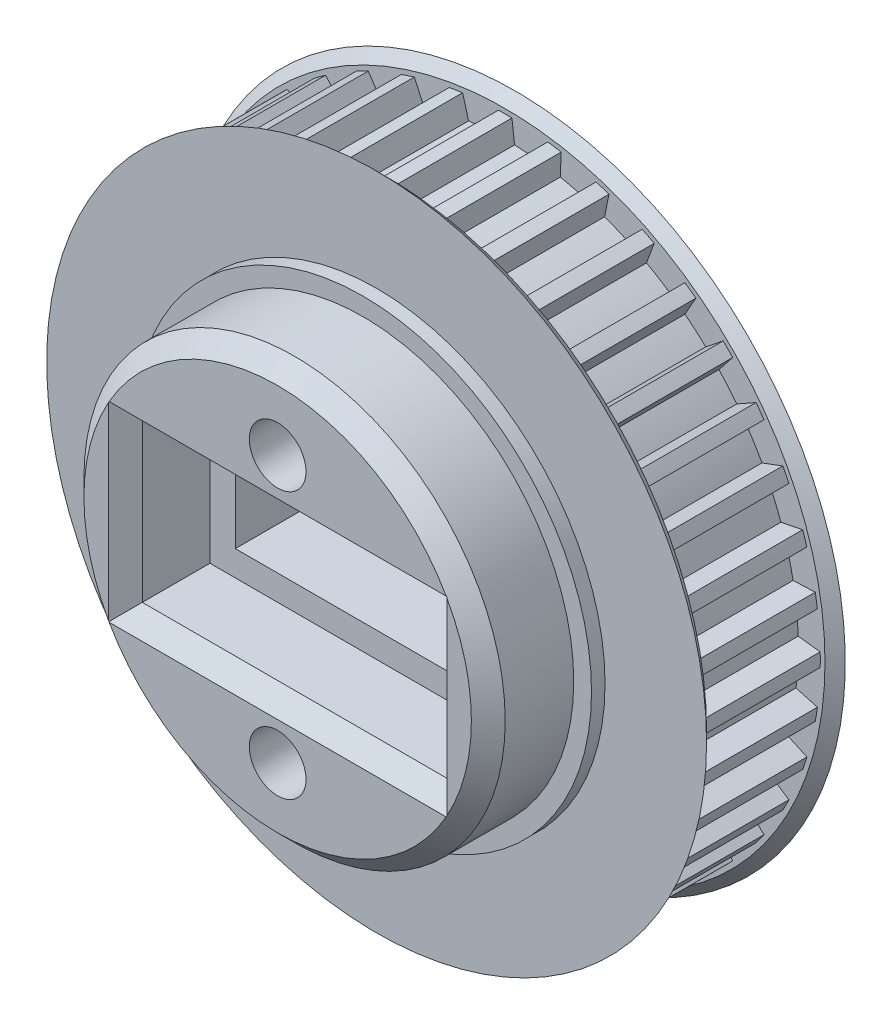
SolidWorks part; units mm, degrees
material "ABS"
ref_plane "Alzado" through (0, 0, 0) normal (0, 0, 1) x (1, 0, 0)
ref_plane "Planta" through (0, 0, 0) normal (0, 1, 0) x (1, 0, 0)
ref_plane "Vista lateral" through (0, 0, 0) normal (1, 0, 0) x (0, 0, -1)
sketch "Croquis1" plane through (0, 0, 0) normal (0, 0, 1) x (1, 0, 0)
  line L0 (0, 0) -> (0, 14.5885) construction
  line L1 (-0.4, 18.6167) -> (-0.55, 17.3123)
  line L2 (0.4, 18.6167) -> (0.55, 17.3123)
  line L3 (3.3074, 18.3249) -> (3.2515, 17.0131)
  line L4 (2.5172, 18.4501) -> (2.165, 17.1852)
  line L5 (6.1333, 17.5819) -> (5.8729, 16.295)
  line L6 (5.3725, 17.8291) -> (4.8267, 16.6349)
  line L7 (8.8082, 16.406) -> (8.3497, 15.1756)
  line L8 (8.0954, 16.7692) -> (7.3695, 15.675)
  line L9 (11.2662, 14.8261) -> (10.6209, 13.6826)
  line L10 (10.619, 15.2963) -> (9.7309, 14.3292)
  line L11 (13.4468, 12.8812) -> (12.6305, 11.8527)
  line L12 (12.8812, 13.4468) -> (11.8527, 12.6305)
  line L13 (15.2963, 10.619) -> (14.3292, 9.7309)
  line L14 (14.8261, 11.2662) -> (13.6826, 10.6209)
  line L15 (16.7692, 8.0954) -> (15.675, 7.3695)
  line L16 (16.406, 8.8082) -> (15.1756, 8.3497)
  line L17 (17.8291, 5.3725) -> (16.6349, 4.8267)
  line L18 (17.5819, 6.1333) -> (16.295, 5.8729)
  line L19 (18.4501, 2.5172) -> (17.1852, 2.165)
  line L20 (18.3249, 3.3074) -> (17.0131, 3.2515)
  line L21 (18.6167, -0.4) -> (17.3123, -0.55)
  line L22 (18.6167, 0.4) -> (17.3123, 0.55)
  line L23 (18.3249, -3.3074) -> (17.0131, -3.2515)
  line L24 (18.4501, -2.5172) -> (17.1852, -2.165)
  line L25 (17.5819, -6.1333) -> (16.295, -5.8729)
  line L26 (17.8291, -5.3725) -> (16.6349, -4.8267)
  line L27 (16.406, -8.8082) -> (15.1756, -8.3497)
  line L28 (16.7692, -8.0954) -> (15.675, -7.3695)
  line L29 (14.8261, -11.2662) -> (13.6826, -10.6209)
  line L30 (15.2963, -10.619) -> (14.3292, -9.7309)
  line L31 (12.8812, -13.4468) -> (11.8527, -12.6305)
  line L32 (13.4468, -12.8812) -> (12.6305, -11.8527)
  line L33 (10.619, -15.2963) -> (9.7309, -14.3292)
  line L34 (11.2662, -14.8261) -> (10.6209, -13.6826)
  line L35 (8.0954, -16.7692) -> (7.3695, -15.675)
  line L36 (8.8082, -16.406) -> (8.3497, -15.1756)
  line L37 (5.3725, -17.8291) -> (4.8267, -16.6349)
  line L38 (6.1333, -17.5819) -> (5.8729, -16.295)
  line L39 (2.5172, -18.4501) -> (2.165, -17.1852)
  line L40 (3.3074, -18.3249) -> (3.2515, -17.0131)
  line L41 (-0.4, -18.6167) -> (-0.55, -17.3123)
  line L42 (0.4, -18.6167) -> (0.55, -17.3123)
  line L43 (-3.3074, -18.3249) -> (-3.2515, -17.0131)
  line L44 (-2.5172, -18.4501) -> (-2.165, -17.1852)
  line L45 (-6.1333, -17.5819) -> (-5.8729, -16.295)
  line L46 (-5.3725, -17.8291) -> (-4.8267, -16.6349)
  line L47 (-8.8082, -16.406) -> (-8.3497, -15.1756)
  line L48 (-8.0954, -16.7692) -> (-7.3695, -15.675)
  line L49 (-11.2662, -14.8261) -> (-10.6209, -13.6826)
  line L50 (-10.619, -15.2963) -> (-9.7309, -14.3292)
  line L51 (-13.4468, -12.8812) -> (-12.6305, -11.8527)
  line L52 (-12.8812, -13.4468) -> (-11.8527, -12.6305)
  line L53 (-15.2963, -10.619) -> (-14.3292, -9.7309)
  line L54 (-14.8261, -11.2662) -> (-13.6826, -10.6209)
  line L55 (-16.7692, -8.0954) -> (-15.675, -7.3695)
  line L56 (-16.406, -8.8082) -> (-15.1756, -8.3497)
  line L57 (-17.8291, -5.3725) -> (-16.6349, -4.8267)
  line L58 (-17.5819, -6.1333) -> (-16.295, -5.8729)
  line L59 (-18.4501, -2.5172) -> (-17.1852, -2.165)
  line L60 (-18.3249, -3.3074) -> (-17.0131, -3.2515)
  line L61 (-18.6167, 0.4) -> (-17.3123, 0.55)
  line L62 (-18.6167, -0.4) -> (-17.3123, -0.55)
  line L63 (-18.3249, 3.3074) -> (-17.0131, 3.2515)
  line L64 (-18.4501, 2.5172) -> (-17.1852, 2.165)
  line L65 (-17.5819, 6.1333) -> (-16.295, 5.8729)
  line L66 (-17.8291, 5.3725) -> (-16.6349, 4.8267)
  line L67 (-16.406, 8.8082) -> (-15.1756, 8.3497)
  line L68 (-16.7692, 8.0954) -> (-15.675, 7.3695)
  line L69 (-14.8261, 11.2662) -> (-13.6826, 10.6209)
  line L70 (-15.2963, 10.619) -> (-14.3292, 9.7309)
  line L71 (-12.8812, 13.4468) -> (-11.8527, 12.6305)
  line L72 (-13.4468, 12.8812) -> (-12.6305, 11.8527)
  line L73 (-10.619, 15.2963) -> (-9.7309, 14.3292)
  line L74 (-11.2662, 14.8261) -> (-10.6209, 13.6826)
  line L75 (-8.0954, 16.7692) -> (-7.3695, 15.675)
  line L76 (-8.8082, 16.406) -> (-8.3497, 15.1756)
  line L77 (-5.3725, 17.8291) -> (-4.8267, 16.6349)
  line L78 (-6.1333, 17.5819) -> (-5.8729, 16.295)
  line L79 (-11.2662, 14.8261) -> (-10.619, 15.2963)
  line L80 (-8.8082, 16.406) -> (-8.0954, 16.7692)
  line L81 (-6.1333, 17.5819) -> (-5.3725, 17.8291)
  line L82 (-2.5172, 18.4501) -> (-2.165, 17.1852)
  line L83 (-3.3074, 18.3249) -> (-3.2515, 17.0131)
  line L84 (-3.3074, 18.3249) -> (-2.5172, 18.4501)
  arc A0 (-17.5819, 6.1333) -> (-17.8291, 5.3725) centre (0, 0) ccw
  arc A1 (2.165, 17.1852) -> (0.55, 17.3123) centre (0, 0) ccw
  arc A2 (-18.3249, 3.3074) -> (-18.4501, 2.5172) centre (0, 0) ccw
  arc A3 (-18.6167, 0.4) -> (-18.6167, -0.4) centre (0, 0) ccw
  arc A4 (-18.4501, -2.5172) -> (-18.3249, -3.3074) centre (0, 0) ccw
  arc A5 (-17.8291, -5.3725) -> (-17.5819, -6.1333) centre (0, 0) ccw
  arc A6 (-16.7692, -8.0954) -> (-16.406, -8.8082) centre (0, 0) ccw
  arc A7 (-15.2963, -10.619) -> (-14.8261, -11.2662) centre (0, 0) ccw
  arc A8 (-13.4468, -12.8812) -> (-12.8812, -13.4468) centre (0, 0) ccw
  arc A9 (-11.2662, -14.8261) -> (-10.619, -15.2963) centre (0, 0) ccw
  arc A10 (-8.8082, -16.406) -> (-8.0954, -16.7692) centre (0, 0) ccw
  arc A11 (3.3074, 18.3249) -> (2.5172, 18.4501) centre (0, 0) ccw
  arc A12 (0.4, 18.6167) -> (-0.4, 18.6167) centre (0, 0) ccw
  arc A13 (-14.8261, 11.2662) -> (-15.2963, 10.619) centre (0, 0) ccw
  arc A14 (-16.406, 8.8082) -> (-16.7692, 8.0954) centre (0, 0) ccw
  arc A15 (-12.8812, 13.4468) -> (-13.4468, 12.8812) centre (0, 0) ccw
  arc A16 (6.1333, 17.5819) -> (5.3725, 17.8291) centre (0, 0) ccw
  arc A17 (8.8082, 16.406) -> (8.0954, 16.7692) centre (0, 0) ccw
  arc A18 (11.2662, 14.8261) -> (10.619, 15.2963) centre (0, 0) ccw
  arc A19 (13.4468, 12.8812) -> (12.8812, 13.4468) centre (0, 0) ccw
  arc A20 (15.2963, 10.619) -> (14.8261, 11.2662) centre (0, 0) ccw
  arc A21 (16.7692, 8.0954) -> (16.406, 8.8082) centre (0, 0) ccw
  arc A22 (17.8291, 5.3725) -> (17.5819, 6.1333) centre (0, 0) ccw
  arc A23 (18.4501, 2.5172) -> (18.3249, 3.3074) centre (0, 0) ccw
  arc A24 (18.6167, -0.4) -> (18.6167, 0.4) centre (0, 0) ccw
  arc A25 (18.3249, -3.3074) -> (18.4501, -2.5172) centre (0, 0) ccw
  arc A26 (12.8812, -13.4468) -> (13.4468, -12.8812) centre (0, 0) ccw
  arc A27 (10.619, -15.2963) -> (11.2662, -14.8261) centre (0, 0) ccw
  arc A28 (8.0954, -16.7692) -> (8.8082, -16.406) centre (0, 0) ccw
  arc A29 (2.5172, -18.4501) -> (3.3074, -18.3249) centre (0, 0) ccw
  arc A30 (-0.4, -18.6167) -> (0.4, -18.6167) centre (0, 0) ccw
  arc A31 (-3.3074, -18.3249) -> (-2.5172, -18.4501) centre (0, 0) ccw
  arc A32 (-6.1333, -17.5819) -> (-5.3725, -17.8291) centre (0, 0) ccw
  arc A33 (14.8261, -11.2662) -> (15.2963, -10.619) centre (0, 0) ccw
  arc A34 (16.406, -8.8082) -> (16.7692, -8.0954) centre (0, 0) ccw
  arc A35 (17.5819, -6.1333) -> (17.8291, -5.3725) centre (0, 0) ccw
  arc A36 (4.8267, 16.6349) -> (3.2515, 17.0131) centre (0, 0) ccw
  arc A37 (7.3695, 15.675) -> (5.8729, 16.295) centre (0, 0) ccw
  arc A38 (-12.6305, 11.8527) -> (-13.6826, 10.6209) centre (0, 0) ccw
  arc A39 (-0.55, 17.3123) -> (-2.165, 17.1852) centre (0, 0) ccw
  arc A40 (-14.3292, 9.7309) -> (-15.1756, 8.3497) centre (0, 0) ccw
  arc A41 (-15.675, 7.3695) -> (-16.295, 5.8729) centre (0, 0) ccw
  arc A42 (-16.6349, 4.8267) -> (-17.0131, 3.2515) centre (0, 0) ccw
  arc A43 (9.7309, 14.3292) -> (8.3497, 15.1756) centre (0, 0) ccw
  arc A44 (11.8527, 12.6305) -> (10.6209, 13.6826) centre (0, 0) ccw
  arc A45 (13.6826, 10.6209) -> (12.6305, 11.8527) centre (0, 0) ccw
  arc A46 (15.1756, 8.3497) -> (14.3292, 9.7309) centre (0, 0) ccw
  arc A47 (16.295, 5.8729) -> (15.675, 7.3695) centre (0, 0) ccw
  arc A48 (17.0131, 3.2515) -> (16.6349, 4.8267) centre (0, 0) ccw
  arc A49 (17.3123, 0.55) -> (17.1852, 2.165) centre (0, 0) ccw
  arc A50 (17.1852, -2.165) -> (17.3123, -0.55) centre (0, 0) ccw
  arc A51 (16.6349, -4.8267) -> (17.0131, -3.2515) centre (0, 0) ccw
  arc A52 (15.675, -7.3695) -> (16.295, -5.8729) centre (0, 0) ccw
  arc A53 (14.3292, -9.7309) -> (15.1756, -8.3497) centre (0, 0) ccw
  arc A54 (12.6305, -11.8527) -> (13.6826, -10.6209) centre (0, 0) ccw
  arc A55 (10.6209, -13.6826) -> (11.8527, -12.6305) centre (0, 0) ccw
  arc A56 (8.3497, -15.1756) -> (9.7309, -14.3292) centre (0, 0) ccw
  arc A57 (5.8729, -16.295) -> (7.3695, -15.675) centre (0, 0) ccw
  arc A58 (3.2515, -17.0131) -> (4.8267, -16.6349) centre (0, 0) ccw
  arc A59 (0.55, -17.3123) -> (2.165, -17.1852) centre (0, 0) ccw
  arc A60 (-2.165, -17.1852) -> (-0.55, -17.3123) centre (0, 0) ccw
  arc A61 (-4.8267, -16.6349) -> (-3.2515, -17.0131) centre (0, 0) ccw
  arc A62 (-7.3695, -15.675) -> (-5.8729, -16.295) centre (0, 0) ccw
  arc A63 (-9.7309, -14.3292) -> (-8.3497, -15.1756) centre (0, 0) ccw
  arc A64 (-11.8527, -12.6305) -> (-10.6209, -13.6826) centre (0, 0) ccw
  arc A65 (-13.6826, -10.6209) -> (-12.6305, -11.8527) centre (0, 0) ccw
  arc A66 (-15.1756, -8.3497) -> (-14.3292, -9.7309) centre (0, 0) ccw
  arc A67 (-16.295, -5.8729) -> (-15.675, -7.3695) centre (0, 0) ccw
  arc A68 (-17.0131, -3.2515) -> (-16.6349, -4.8267) centre (0, 0) ccw
  arc A69 (-17.3123, -0.55) -> (-17.1852, -2.165) centre (0, 0) ccw
  arc A70 (-17.1852, 2.165) -> (-17.3123, 0.55) centre (0, 0) ccw
  arc A71 (5.3725, -17.8291) -> (6.1333, -17.5819) centre (0, 0) ccw
  circle A72 centre (0, 0) radius 2
  arc A73 (-5.8729, 16.295) -> (-7.3695, 15.675) centre (0, 0) ccw
  arc A74 (-8.3497, 15.1756) -> (-9.7309, 14.3292) centre (0, 0) ccw
  arc A75 (-10.6209, 13.6826) -> (-11.8527, 12.6305) centre (0, 0) ccw
  arc A76 (-3.2515, 17.0131) -> (-4.8267, 16.6349) centre (0, 0) ccw
  point P151 (0, 0)
  dimension "D1" = 1.3
  dimension "D6" = 4
  dimension "D2" = 1.1
  dimension "D3" = 0.8
  dimension "D5" = 1.62
  dimension "D4" = 40
extrude "Saliente-Extruir1" add sketch "Croquis1" along normal blind 7
sketch "Croquis2" plane through (0, 0, 7) normal (0, 0, 1) x (1, 0, 0)
  circle A0 centre (0, 0) radius 19.5
  circle A1 centre (0, 0) radius 2
  circle A2 centre (0, 0) radius 2 construction
  dimension "D1" = 39
extrude "Saliente-Extruir2" add sketch "Croquis2" along normal blind 0.6
sketch "Croquis3" plane through (0, 0, 7.6) normal (0, 0, 1) x (1, 0, 0)
  circle A0 centre (0, 0) radius 2
  circle A1 centre (0, 0) radius 12.45
  circle A3 centre (0, 0) radius 2 construction
  dimension "D1" = 24.9
sketch "Croquis4" plane through (0, 0, 0) normal (0, 0, -1) x (-1, 0, 0)
  circle A0 centre (0, 0) radius 2
  circle A1 centre (0, 0) radius 12.45
  circle A2 centre (0, 0) radius 2 construction
  dimension "D1" = 24.9
extrude "Saliente-Extruir4" add sketch "Croquis4" along normal blind 5.8
sketch "Croquis6" plane through (0, 0, 0) normal (0, 0, -1) x (-1, 0, 0)
  circle A0 centre (0, 0) radius 19.5
  circle A1 centre (0, 0) radius 2
  circle A2 centre (0, 0) radius 2 construction
  dimension "D1" = 39
extrude "Saliente-Extruir6" add sketch "Croquis6" along normal blind 0.6
sketch "Croquis5" plane through (0, 0, -0.6) normal (0, 0, -1) x (-1, 0, 0)
  circle A0 centre (0, 0) radius 2
  circle A1 centre (0, 0) radius 13.5
  circle A2 centre (0, 0) radius 2 construction
  dimension "D1" = 27
extrude "Saliente-Extruir5" add sketch "Croquis5" along normal blind 0.6
extrude "Saliente-Extruir7" add sketch "Croquis3" along normal blind 5.85
chamfer "Chaflán4" distance 1 angle 45 2 edges at (-12.45, 0, -5.8) (12.45, 0, 13.45)
sketch "Croquis7" plane through (0, 0, 7.6) normal (0, 0, 1) x (1, 0, 0)
  circle A0 centre (0, 0) radius 2
  circle A1 centre (0, 0) radius 13.5
  circle A2 centre (0, 0) radius 2 construction
  dimension "D1" = 27
extrude "Saliente-Extruir8" add sketch "Croquis7" along normal blind 0.8
sketch "Croquis8" plane through (0, 0, 0) normal (0, 0, 1) x (1, 0, 0)
  line L0 (0, 0) -> (6.706, 0) construction
  line L1 (-7.5, 3.15) -> (7.5, 3.15)
  line L2 (-7.5, 3.15) -> (-7.5, -3.15)
  line L3 (-7.5, -3.15) -> (7.5, -3.15)
  line L4 (7.5, 3.15) -> (7.5, -3.15)
  line L5 (-7.5, 3.15) -> (7.5, -3.15) construction
  line L6 (-7.5, -3.15) -> (7.5, 3.15) construction
  circle A0 centre (0, 7.8756) radius 1.675
  circle A1 centre (0, -7.8756) radius 1.675
  point P0 (0, 0)
  dimension "D1" = 3.35
  dimension "D2" = 6.3
  dimension "D3" = 15
extrude "Cortar-Extruir1" cut sketch "Croquis8" against normal through all both and the other way through all
sketch "Croquis9" plane through (0, 0, -5.8) normal (0, 0, -1) x (-1, 0, 0)
  line L1 (2.3383, 3.8256) -> (4.6765, 7.8756)
  line L2 (4.6765, 7.8756) -> (2.3383, 11.9256)
  line L3 (2.3383, 11.9256) -> (-2.3383, 11.9256)
  line L4 (-2.3383, 11.9256) -> (-4.6765, 7.8756)
  line L5 (-4.6765, 7.8756) -> (-2.3383, 3.8256)
  line L6 (-2.3383, 3.8256) -> (2.3383, 3.8256)
  line L7 (2.3383, -11.9256) -> (4.6765, -7.8756)
  line L8 (4.6765, -7.8756) -> (2.3383, -3.8256)
  line L9 (2.3383, -3.8256) -> (-2.3383, -3.8256)
  line L10 (-2.3383, -3.8256) -> (-4.6765, -7.8756)
  line L11 (-4.6765, -7.8756) -> (-2.3383, -11.9256)
  line L12 (-2.3383, -11.9256) -> (2.3383, -11.9256)
  circle A0 centre (0, 7.8756) radius 4.05 construction
  circle A1 centre (0, -7.8756) radius 4.05 construction
  dimension "D1" = 8.1
extrude "Cortar-Extruir2" cut sketch "Croquis9" against normal blind 5
fillet "Redondeo1" radius 2.5 12 edges at (3.5074, -9.9006, -0.8) (3.5074, -5.8506, -0.8) (0, -3.8256, -0.8) (-3.5074, -5.8506, -0.8) (0, -11.9256, -0.8) (-3.5074, -9.9006, -0.8) (-3.5074, 5.8506, -0.8) (-3.5074, 9.9006, -0.8) (0, 11.9256, -0.8) (3.5074, 9.9006, -0.8) (3.5074, 5.8506, -0.8) (0, 3.8256, -0.8)
sketch "Croquis10" plane through (0, 0, 13.45) normal (0, 0, 1) x (1, 0, 0)
  line L0 (7.5, 3.15) -> (-7.5, 3.15) construction
  line L1 (9, 4.65) -> (-9, 4.65)
  line L2 (9, 4.65) -> (9, -4.65)
  line L3 (9, -4.65) -> (-9, -4.65)
  line L4 (-9, 4.65) -> (-9, -4.65)
  line L5 (9, 4.65) -> (-9, -4.65) construction
  line L6 (9, -4.65) -> (-9, 4.65) construction
  line L7 (-7.5, 3.15) -> (-7.5, -3.15) construction
  point P0 (0, 0)
  dimension "D1" = 1.5
  dimension "D2" = 1.5
extrude "Cortar-Extruir3" cut sketch "Croquis10" against normal blind 5
chamfer "Chaflán5" distance 1 angle 45 8 edges at (-7.5, 0, -5.8) (0, 3.15, -5.8) (7.5, 0, -5.8) (0, -3.15, -5.8) (9, 0, 13.45) (0, 4.65, 13.45) (-9, 0, 13.45) (0, -4.65, 13.45)
chamfer "Chaflán6" distance 0.6 angle 45 2 edges at (19.5, 0, 7) (-19.5, 0, 0)
